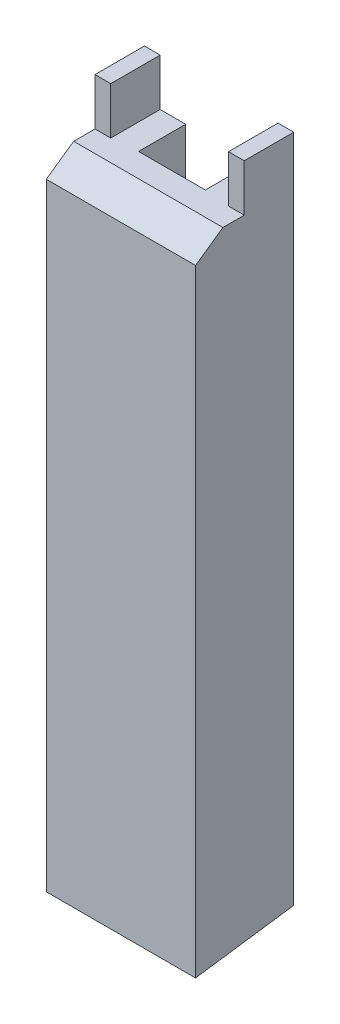
SolidWorks part; units mm, degrees
ref_plane "Front Plane" through (0, 0, 0) normal (0, 0, 1) x (1, 0, 0)
ref_plane "Top Plane" through (0, 0, 0) normal (0, 1, 0) x (1, 0, 0)
ref_plane "Right Plane" through (0, 0, 0) normal (1, 0, 0) x (0, 0, -1)
sketch "Sketch1" plane through (0, 0, 0) normal (0, 0, 1) x (1, 0, 0)
  line L1 (-9.7143, 13.1912) -> (9.2857, 13.1912)
  line L2 (-9.7143, 13.1912) -> (-9.7143, -67.8088)
  line L3 (-9.7143, -67.8088) -> (9.2857, -67.8088)
  line L4 (9.2857, 13.1912) -> (9.2857, -67.8088)
  dimension "D1" = 19
  dimension "D2" = 81
extrude "Boss-Extrude1" add sketch "Sketch1" along normal blind 12.5
sketch "Sketch2" plane through (0, 0, 0) normal (0, 0, -1) x (-1, 0, 0)
  line L0 (0.2143, 16.8694) -> (0.2143, -71.6226) construction
  line L5 (-9.2857, -67.8088) -> (-9.2857, 13.1912) construction
  line L6 (9.7143, 13.1912) -> (9.7143, -67.8088) construction
  line L7 (-9.2857, 13.1912) -> (9.7143, 13.1912) construction
  line L8 (-4.0357, 13.1912) -> (4.4643, 13.1912)
  line L9 (-4.0357, 13.1912) -> (-4.0357, -67.8088)
  line L10 (-4.0357, -67.8088) -> (4.4643, -67.8088)
  line L11 (4.4643, 13.1912) -> (4.4643, -67.8088)
  line L13 (9.7143, -67.8088) -> (-9.2857, -67.8088) construction
  dimension "D1" = 8.5
extrude "Cut-Extrude1" cut sketch "Sketch2" against normal blind 6
ref_plane "Plane1" through (0, -64.7727, -9.1032) normal (0, -0.9903, -0.1392) x (1, 0, 0)
sketch "Sketch3" plane through (0, -64.7727, -9.1032) normal (0, -0.9903, -0.1392) x (1, 0, 0)
  line L9 (-16.6295, 27.5301) -> (15.1549, 27.5301)
  line L10 (-16.6295, 27.5301) -> (-16.6295, 7.4455)
  line L11 (-16.6295, 7.4455) -> (15.1549, 7.4455)
  line L12 (15.1549, 27.5301) -> (15.1549, 7.4455)
extrude "Cut-Extrude2" cut sketch "Sketch3" along normal through all
ref_plane "Plane2" through (0, 14.7245, 10.3102) normal (0, 0.8192, 0.5736) x (-1, 0, 0)
ref_plane "Plane3" through (0, 13.0862, 9.163) normal (0, 0.8192, 0.5736) x (-1, 0, 0)
sketch "Sketch4" plane through (0, 13.0862, 9.163) normal (0, 0.8192, 0.5736) x (-1, 0, 0)
  line L1 (-13.8089, 11.272) -> (13.9843, 11.272)
  line L2 (-13.8089, 11.272) -> (-13.8089, -4.4518)
  line L3 (-13.8089, -4.4518) -> (13.9843, -4.4518)
  line L4 (13.9843, 11.272) -> (13.9843, -4.4518)
extrude "Cut-Extrude3" cut sketch "Sketch4" along normal through all
sketch "Sketch5" plane through (0, 13.1912, 0) normal (0, 1, 0) x (1, 0, 0)
  line L1 (-9.7143, 0) -> (-7.7143, 0)
  line L2 (-9.7143, 0) -> (-9.7143, -6.3)
  line L3 (-9.7143, -6.3) -> (-7.7143, -6.3)
  line L4 (-7.7143, 0) -> (-7.7143, -6.3)
  line L5 (9.2857, 0) -> (7.2857, 0)
  line L6 (9.2857, 0) -> (9.2857, -6.3)
  line L7 (9.2857, -6.3) -> (7.2857, -6.3)
  line L8 (7.2857, 0) -> (7.2857, -6.3)
  dimension "D1" = 2
  dimension "D2" = 6.3
  dimension "D3" = 6.3
  dimension "D4" = 2
extrude "Boss-Extrude2" add sketch "Sketch5" along normal blind 6
